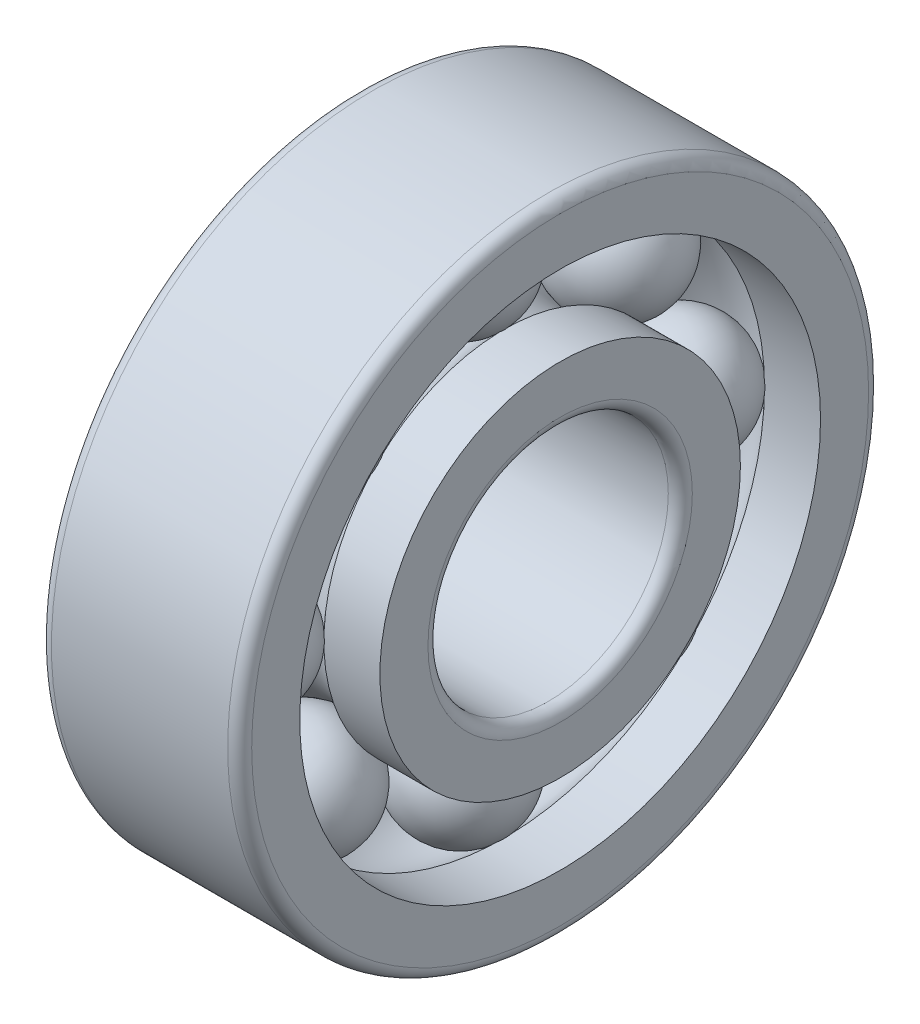
SolidWorks part; units mm, degrees
ref_plane "Plane1" through (0, 0, 0) normal (0, 0, 1) x (1, 0, 0)
ref_plane "Plane2" through (0, 0, 0) normal (0, 1, 0) x (1, 0, 0)
ref_plane "Plane3" through (0, 0, 0) normal (1, 0, 0) x (0, 0, -1)
ref_axis "Axis1" through (-50, 0, 0) along (1, 0, 0)
sketch "BalDetSke" plane through (0, 0, 0) normal (0, 0, 1) x (1, 0, 0)
  line L0 (-3, 11) -> (3, 11)
  line L1 (-1.905, 11) -> (1.905, 11) construction
  line L2 (0, 0) -> (0, 25) construction
  arc A0 (3, 11) -> (-3, 11) centre (0, 11) cw
  dimension "Ball_diameter" = 6
  dimension "BallCLRad" = 11
revolve "BallDetailed" add sketch "BalDetSke" angle 360 about L1 reverse direction yes
sketch "InnRacSke" plane through (0, 0, 0) normal (0, 0, 1) x (1, 0, 0)
  line L0 (-2.2024, 9) -> (-5, 9)
  line L1 (-5, 9) -> (-5, 6.6)
  line L2 (-4.4, 6) -> (4.4, 6)
  line L3 (5, 6.6) -> (5, 9)
  line L4 (5, 9) -> (2.2024, 9)
  line L5 (-20.6375, 0) -> (20.6375, 0) construction
  line L6 (0, 0) -> (0, 30) construction
  arc A0 (-5, 6.6) -> (-4.4, 6) centre (-4.4, 6.6) ccw
  arc A1 (4.4, 6) -> (5, 6.6) centre (4.4, 6.6) ccw
  arc A2 (2.2024, 9) -> (-2.2024, 9) centre (0, 11) cw
  dimension "Fillet_radius" = 0.6
  dimension "Ball_diameter" = 5.95
  dimension "ID" = 12
  dimension "OD" = 18
  dimension "Width" = 10
  dimension "BallCLRad" = 11
revolve "InnerRace" add sketch "InnRacSke" angle 360 about L5 reverse direction yes
sketch "OutRacSke" plane through (0, 0, 0) normal (0, 0, 1) x (1, 0, 0)
  line L0 (-2.2024, 13) -> (-5, 13)
  line L1 (-5, 13) -> (-5, 15.4)
  line L2 (-4.4, 16) -> (4.4, 16)
  line L3 (5, 15.4) -> (5, 13)
  line L4 (5, 13) -> (2.2024, 13)
  line L5 (-20.6375, 0) -> (20.6375, 0) construction
  line L6 (0, 0) -> (0, 30) construction
  arc A0 (-5, 15.4) -> (-4.4, 16) centre (-4.4, 15.4) cw
  arc A1 (4.4, 16) -> (5, 15.4) centre (4.4, 15.4) cw
  arc A2 (2.2024, 13) -> (-2.2024, 13) centre (0, 11) ccw
  dimension "Fillet_radius" = 0.6
  dimension "Ball_diameter" = 5.95
  dimension "OD" = 32
  dimension "ID" = 26
  dimension "Width" = 10
  dimension "BallCLRad" = 11
revolve "OuterRace" add sketch "OutRacSke" angle 360 about L5 reverse direction yes
pattern_circular "Répétition circulaire1" count 8 over 360 about axis through (-20.6375, 0, 0) along (1, 0, 0) reverse direction yes of bodies 102
